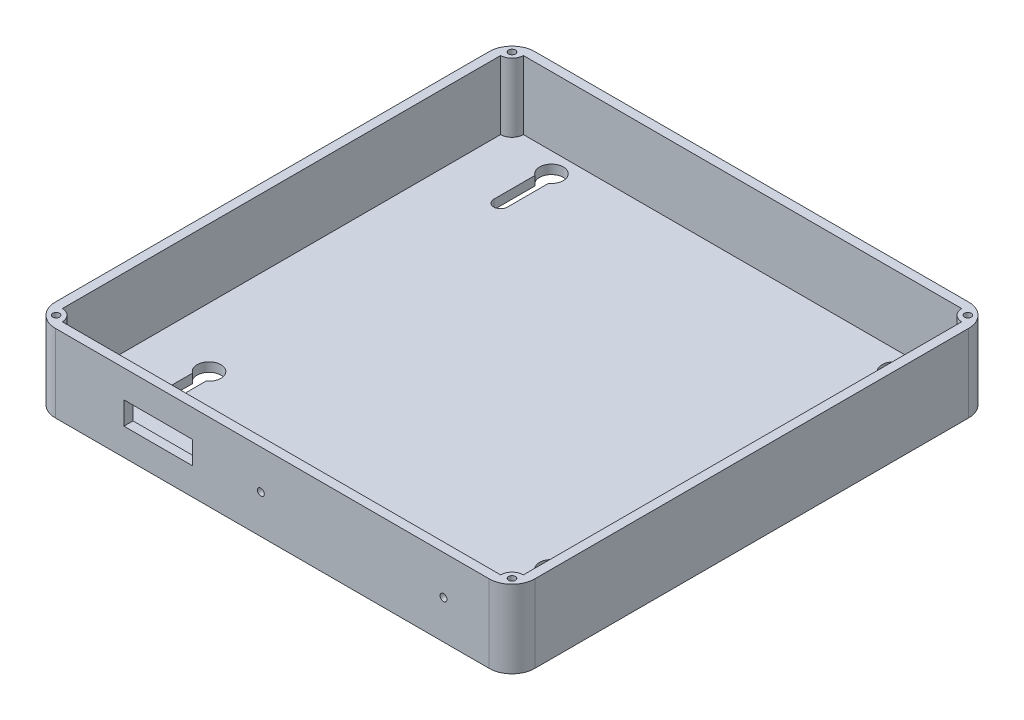
SolidWorks part; units mm, degrees
ref_plane "Front Plane" through (0, 0, 0) normal (0, 0, 1) x (1, 0, 0)
ref_plane "Top Plane" through (0, 0, 0) normal (0, 1, 0) x (1, 0, 0)
ref_plane "Right Plane" through (0, 0, 0) normal (1, 0, 0) x (0, 0, -1)
sketch "Sketch1" plane through (0, 0, 0) normal (0, 1, 0) x (1, 0, 0)
  line L0 (-101, -101) -> (-101, 101)
  line L1 (-105, -105) -> (105, -105)
  line L2 (-105, -105) -> (-105, 105)
  line L3 (-105, 105) -> (105, 105)
  line L4 (105, -105) -> (105, 105)
  line L5 (-101, 101) -> (101, 101)
  line L6 (101, -101) -> (101, 101)
  line L7 (-101, -101) -> (101, -101)
  point P0 (0, 0)
  point P6 (0, 105)
  point P7 (-105, 0)
  dimension "D1" = 210
  dimension "D2" = 210
  dimension "D3" = 4
extrude "Base" add sketch "Sketch1" along normal blind 4 contours L1 L4 L3 L2
extrude "Walls" add sketch "Sketch1<3>" along normal blind 30 from surface starting at face at (0, 4, 0)
sketch "Sketch1<3>" plane through (0, 0, 0) normal (0, 1, 0) x (1, 0, 0) same geometry as "Sketch1"
sketch "Sketch2" plane through (0, 34, 0) normal (0, 1, 0) x (1, 0, 0)
  line L0 (-101, 101) -> (-101, 96)
  line L1 (-101, 101) -> (-101, -101) construction
  line L2 (-101, 101) -> (-96, 101)
  line L3 (101, 101) -> (-101, 101) construction
  line L12 (-101, 101) -> (-97.4645, 97.4645) construction
  line L27 (-2.2, 0) -> (2.2, 0) construction
  line L28 (-101, -101) -> (-101, -96)
  line L29 (-101, -101) -> (-96, -101)
  line L30 (0, -2.2) -> (0, 2.2) construction
  line L31 (101, 101) -> (101, 96)
  line L32 (101, 101) -> (96, 101)
  line L33 (101, -101) -> (96, -101)
  line L34 (101, -101) -> (101, -96)
  arc A0 (-101, 96) -> (-96, 101) centre (-101, 101) ccw
  circle A18 centre (-99.8333, 99.8333) radius 1.5
  arc A19 (-101, -96) -> (-96, -101) centre (-101, -101) cw
  circle A20 centre (-99.8333, -99.8333) radius 1.5
  arc A21 (101, 96) -> (96, 101) centre (101, 101) cw
  circle A22 centre (99.8333, 99.8333) radius 1.5
  circle A23 centre (99.8333, -99.8333) radius 1.5
  arc A24 (101, -96) -> (96, -101) centre (101, -101) ccw
  dimension "D2" = 1.65
  dimension "D3" = 3
  dimension "D1" = 5
extrude "ScrewMounts" add sketch "Sketch2" against normal up to surface (30 mm away) contours A0 L2 L0 | A20 | L28 A19 L29 | L33 A24 L34 | L31 A21 L32 up to face at (0, 4, 0)
extrude "ScrewHoles" cut sketch "Sketch2<5>" against normal blind 12.5 contours A23 | A18 | A20 | A22
sketch "Sketch2<5>" plane through (0, 34, 0) normal (0, 1, 0) x (1, 0, 0) same geometry as "Sketch2"
fillet "RoundedCorners" radius 10 4 edges at (-105, 17, -105) (105, 17, -105) (105, 17, 105) (-105, 17, 105)
sketch "Sketch3" plane through (0, 0, 0) normal (0, -1, 0) x (1, 0, 0)
  line L0 (-77.985, 80) -> (-77.985, 61.974)
  line L1 (-72.015, 80) -> (-72.015, 61.974)
  line L2 (-105, 95) -> (-105, -95) construction
  line L3 (-95, 105) -> (95, 105) construction
  line L4 (0, -2.2) -> (0, 2.2) construction
  line L5 (77.985, 80) -> (77.985, 61.974)
  line L6 (72.015, 80) -> (72.015, 61.974)
  line L7 (-75, 57.71) -> (75, 57.71) construction
  line L8 (-75, 57.71) -> (-75, -92.29) construction
  line L9 (72.015, -70) -> (72.015, -88.026)
  line L10 (-77.985, -70) -> (-77.985, -88.026)
  line L11 (-72.015, -70) -> (-72.015, -88.026)
  line L12 (77.985, -70) -> (77.985, -88.026)
  arc A0 (-77.985, 61.974) -> (-72.015, 61.974) centre (-75, 57.71) ccw
  arc A1 (-72.015, 80) -> (-77.985, 80) centre (-75, 80) ccw
  arc A2 (72.015, 80) -> (77.985, 80) centre (75, 80) cw
  arc A3 (77.985, 61.974) -> (72.015, 61.974) centre (75, 57.71) cw
  arc A6 (-77.985, -88.026) -> (-72.015, -88.026) centre (-75, -92.29) ccw
  arc A7 (-77.985, -70) -> (-72.015, -70) centre (-75, -70) cw
  arc A8 (77.985, -70) -> (72.015, -70) centre (75, -70) ccw
  arc A9 (77.985, -88.026) -> (72.015, -88.026) centre (75, -92.29) cw
  dimension "D2" = 10.41
  dimension "D3" = 5.97
  dimension "D7" = 150
  dimension "D1" = 22.29
  dimension "D4" = 30
  dimension "D5" = 25
  dimension "D6" = 150
extrude "BackHoleMounts" cut sketch "Sketch3" against normal up to surface (4 mm away) up to face at (0, 4, 0)
sketch "Sketch4" plane through (0, 0, 105) normal (0, 0, 1) x (1, 0, 0)
  line L0 (-95, 0) -> (95, 0) construction
  line L1 (95, 0) -> (95, 34) construction
  line L3 (-65, 11.9) -> (-35, 11.9)
  line L4 (-65, 11.9) -> (-65, 21.9)
  line L5 (-65, 21.9) -> (-35, 21.9)
  line L6 (-35, 11.9) -> (-35, 21.9)
  circle A0 centre (75, 16.9) radius 1.5
  circle A1 centre (-5, 16.9) radius 1.5
  point P6 (-35, 16.9)
  dimension "D2" = 3
  dimension "D1" = 16.9
  dimension "D3" = 80
  dimension "D4" = 20
  dimension "D5" = 30
  dimension "D6" = 10
  dimension "D7" = 30
extrude "BatteryPack" cut sketch "Sketch4" against normal up to surface (4 mm away) up to face at (0, 19, 101)
